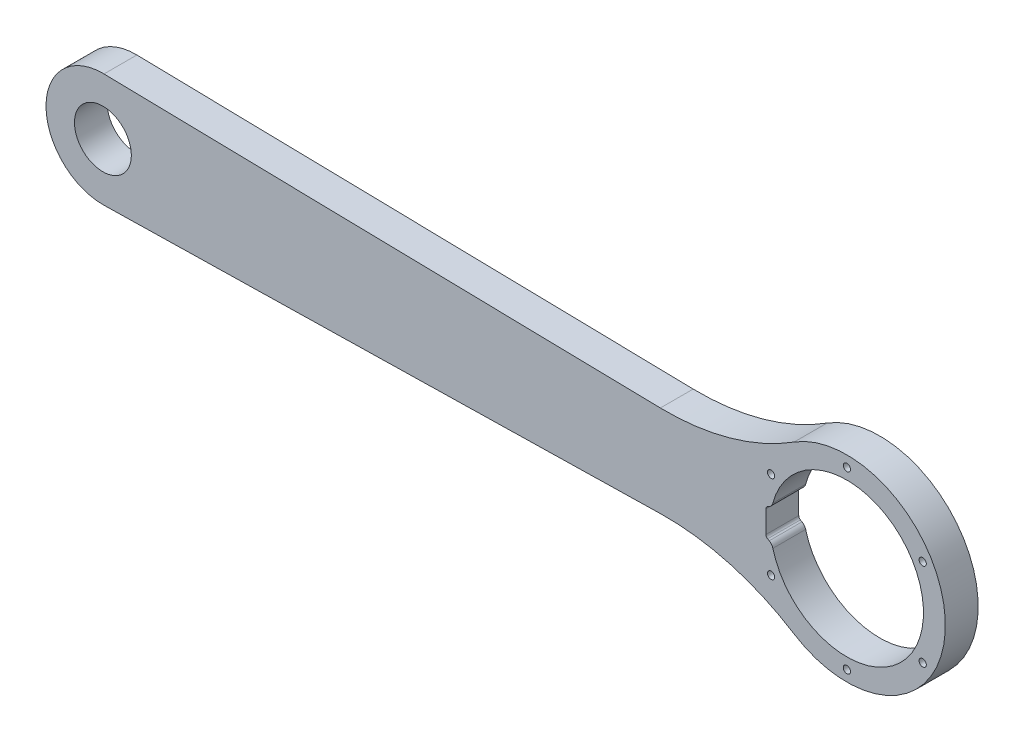
SolidWorks part; units mm, degrees
ref_plane "前视基准面" through (0, 0, 0) normal (0, 0, 1) x (1, 0, 0)
ref_plane "上视基准面" through (0, 0, 0) normal (0, 1, 0) x (1, 0, 0)
ref_plane "右视基准面" through (0, 0, 0) normal (1, 0, 0) x (0, 0, -1)
sketch "草图1" plane through (0, 0, 0) normal (0, 0, 1) x (1, 0, 0)
  line L0 (0, 0) -> (0, 46.9214) construction
  line L1 (0, 0) -> (75.8039, 0) construction
  line L2 (-85.2451, 20.9004) -> (-339.4791, 25.9948)
  line L3 (-85.2451, -20.9004) -> (-339.4791, -25.9948)
  line L4 (-35.5001, 6.7904) -> (-36.238, 6.3734)
  line L5 (-37, 5.0675) -> (-37, -5.0675)
  line L8 (-30.9669, 5.9447) -> (-28.6669, 5.9455) construction
  line L9 (-35.5001, -6.7904) -> (-36.238, -6.3734)
  line L10 (-29.6741, 7.5384) -> (-26.4741, 7.5394) construction
  circle A0 centre (0, 40) radius 1.65
  arc A1 (0, 38.35) -> (0, 41.65) centre (0, 40) ccw construction
  circle A2 centre (34.641, 20) radius 1.65
  circle A3 centre (34.641, -20) radius 1.65
  arc A4 (34.641, 18.35) -> (34.641, 21.65) centre (34.641, 20) ccw construction
  circle A5 centre (0, -40) radius 1.65
  arc A6 (0, -41.65) -> (0, -38.35) centre (0, -40) ccw construction
  circle A7 centre (-34.641, 20) radius 1.65
  arc A8 (-34.641, 21.65) -> (-34.641, 18.35) centre (-34.641, 20) ccw construction
  circle A9 centre (-34.641, -20) radius 1.65
  circle A10 centre (0, 0) radius 35 construction
  arc A12 (-33.8381, 8.9432) -> (-33.8381, -8.9432) centre (0, 0) cw
  arc A13 (-24.1088, 37.9969) -> (-24.1088, -37.9969) centre (0, 0) cw
  circle A14 centre (-340, 0) radius 13
  arc A15 (-85.2451, -20.9004) -> (-24.1088, -37.9969) centre (-83.0414, -130.8783) cw
  arc A16 (-24.1088, 37.9969) -> (-85.2451, 20.9004) centre (-83.0414, 130.8783) cw
  arc A17 (-339.4791, 25.9948) -> (-339.4791, -25.9948) centre (-340, 0) ccw
  arc A18 (-35.5001, -6.7904) -> (-33.8381, -8.9432) centre (-37.2219, -9.8375) cw
  arc A19 (-33.8381, 8.9432) -> (-35.5001, 6.7904) centre (-37.2219, 9.8375) cw
  arc A20 (-36.238, -6.3734) -> (-37, -5.0675) centre (-35.5, -5.0675) cw
  arc A21 (-36.238, 6.3734) -> (-37, 5.0675) centre (-35.5, 5.0675) ccw
  point P48 (-40.3113, -20)
  point P51 (-40.3113, 20)
  point P60 (-37, 0)
  point P63 (-35, 0)
  point P70 (-34.1789, -7.537)
  point P73 (-34.1789, 7.537)
  point P76 (-37, -5.9428)
  point P79 (-37, 5.9428)
  dimension "D1" = 70
  dimension "D2" = 45
  dimension "D4" = 110
  dimension "D5" = 26
  dimension "D7" = 26
  dimension "D9" = 3.5
  dimension "D10" = 1.5
  dimension "D3" = 20
  dimension "D6" = 340
  dimension "D8" = 2
extrude "凸台-拉伸1" add sketch "草图1" along normal blind 15
sketch "草图2" plane through (0, 0, 0) normal (0, 0, 1) x (1, 0, 0)
  line L0 (-376.6145, -430.0012) -> (356.6217, 230.2077) construction
